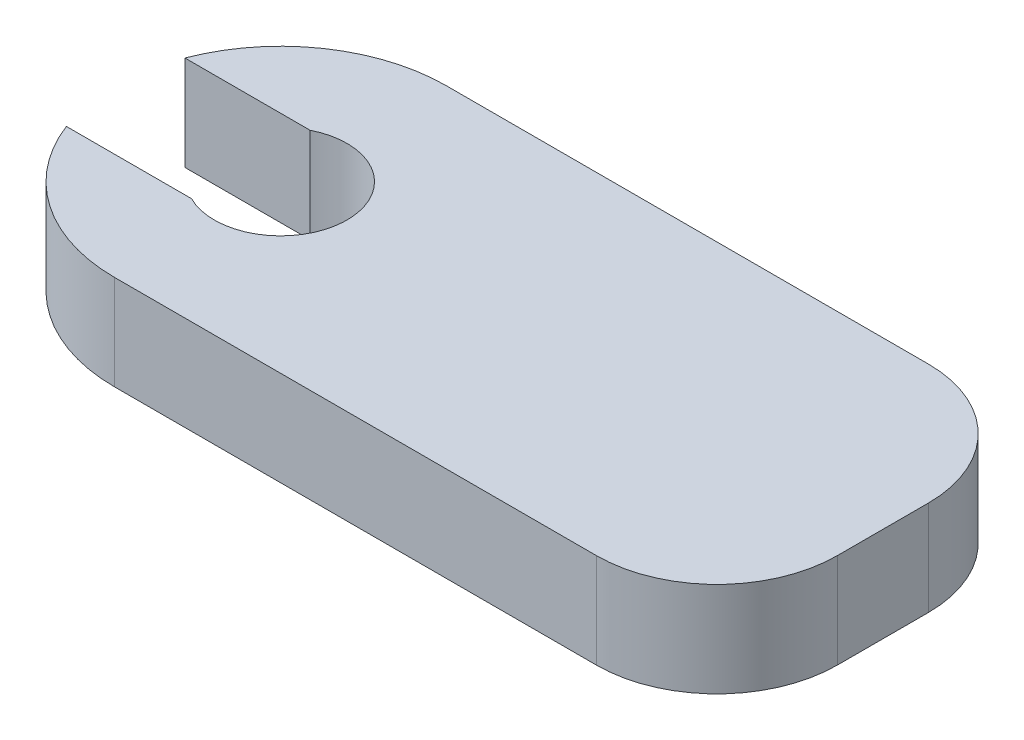
SolidWorks part; units mm, degrees
ref_plane "Front Plane" through (0, 0, 0) normal (0, 0, 1) x (1, 0, 0)
ref_plane "Top Plane" through (0, 0, 0) normal (0, 1, 0) x (1, 0, 0)
ref_plane "Right Plane" through (0, 0, 0) normal (1, 0, 0) x (0, 0, -1)
sketch "Sketch1" plane through (0, 0, 0) normal (0, 1, 0) x (1, 0, 0)
  line L0 (-3.2692, 1.25) -> (-0.6305, 1.25)
  line L1 (-3.2692, -1.25) -> (-0.6305, -1.25)
  line L2 (0, 3.5) -> (10.16, 3.5)
  line L3 (12.7, 0.96) -> (12.7, -0.96)
  line L4 (10.16, -3.5) -> (0, -3.5)
  circle A0 centre (0, 0) radius 1.4
  circle A1 centre (0, 0) radius 3.5
  arc A2 (12.7, -0.96) -> (10.16, -3.5) centre (10.16, -0.96) cw
  arc A3 (10.16, 3.5) -> (12.7, 0.96) centre (10.16, 0.96) cw
  dimension "D1" = 2.8
  dimension "D3" = 7
  dimension "D5" = 2.54
  dimension "D2" = 2.5
  dimension "D4" = 12.7
extrude "Boss-Extrude1" add sketch "Sketch1" along normal blind 2 contours L1 A1 L0 A0 | A1 L4 L3 L2 region at (-1.9291, 0, -2.8029) region at (7.51, 0, 0)
